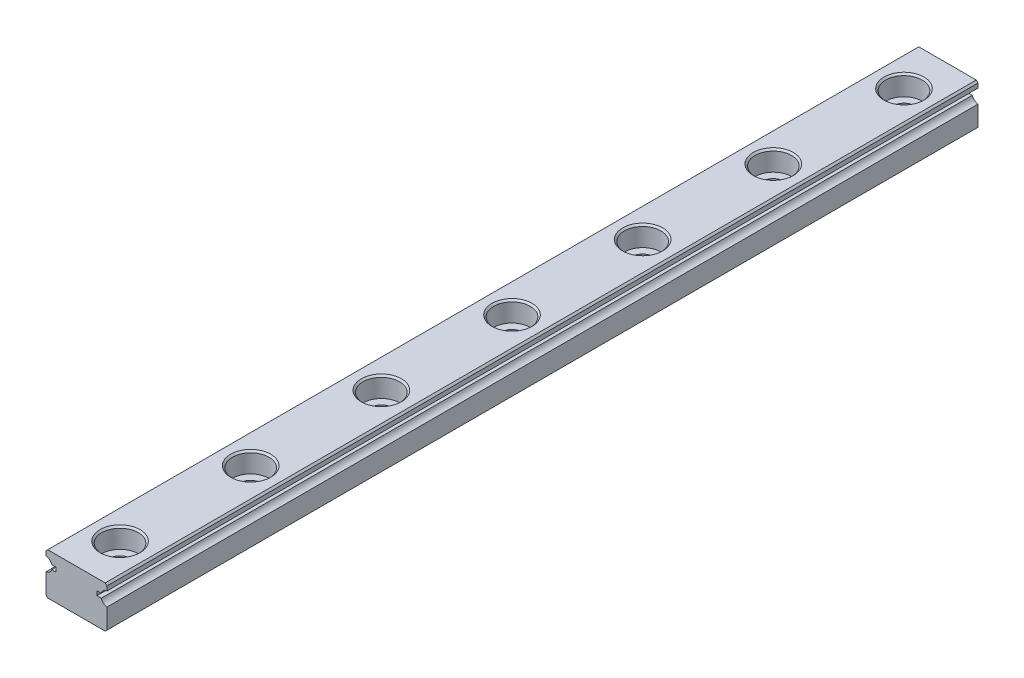
SolidWorks part; units mm, degrees
ref_plane "Спереди" through (0, 0, 0) normal (0, 0, 1) x (1, 0, 0)
ref_plane "Сверху" through (0, 0, 0) normal (0, 1, 0) x (1, 0, 0)
ref_plane "Справа" through (0, 0, 0) normal (1, 0, 0) x (0, 0, -1)
sketch "Sketch1" plane through (0, 0, 0) normal (0, 0, 1) x (1, 0, 0)
  line L0 (0, 0) -> (0, 4.3706) construction
  line L1 (-3.3, -2.4) -> (3.3, -2.4)
  line L2 (-3.5, -2.2) -> (-3.5, 0.1063)
  line L3 (-3.3, 2.4) -> (3.3, 2.4)
  line L4 (3.5, -2.2) -> (3.5, 0.1063)
  line L5 (-3.5, -2.4) -> (3.5, 2.4) construction
  line L6 (-3.5, 2.4) -> (3.5, -2.4) construction
  line L7 (-3.5, 1.6937) -> (-3.5, 2.2)
  line L8 (3.5, 1.6937) -> (3.5, 2.2)
  line L9 (-3.5, -2.2) -> (-3.3, -2.4)
  line L10 (3.3, -2.4) -> (3.5, -2.2)
  line L11 (3.3, 2.4) -> (3.5, 2.2)
  line L12 (-3.5, 2.2) -> (-3.3, 2.4)
  line L13 (2.8401, 0.65) -> (2.3401, 0.65)
  line L14 (-2.8401, 0.65) -> (-2.3401, 0.65)
  line L15 (2.3401, 0.65) -> (2.3401, 1.15)
  line L16 (-2.8401, 1.15) -> (-2.3401, 1.15)
  line L17 (-2.3401, 0.65) -> (-2.3401, 1.15)
  line L18 (2.8401, 1.15) -> (2.3401, 1.15)
  arc A0 (-3.5, 1.6937) -> (-2.8401, 1.15) centre (-3.6, 0.9) cw
  arc A1 (3.5, 1.6937) -> (2.8401, 1.15) centre (3.6, 0.9) ccw
  arc A2 (-2.8401, 0.65) -> (-3.5, 0.1063) centre (-3.6, 0.9) cw
  arc A3 (2.8401, 0.65) -> (3.5, 0.1063) centre (3.6, 0.9) ccw
  point P0 (0, 0)
  dimension "D4" = 0.8
  dimension "D5" = 0.1
  dimension "D1" = 7
  dimension "D2" = 4.8
  dimension "D3" = 1.5
  dimension "D6" = 0.5
  dimension "D7" = 0.5
extrude "Extrude1" add sketch "Sketch1" along normal blind 150
sketch "Sketch2" plane through (0, 2.4, 0) normal (0, 1, 0) x (1, 0, 0)
  line L0 (0, 0) -> (0, -5) construction
  circle A0 centre (0, -5) radius 1.2
  circle A1 centre (0, -5) radius 2.1
  dimension "D1" = 2.4
  dimension "D2" = 4.2
  dimension "D3" = 5
extrude "Extrude2" cut sketch "Sketch2" against normal up to next contours A0 region at (0, 2.4, 5)
extrude "Extrude4" cut sketch "Sketch" against normal blind 2.3
sketch "Sketch" plane through (0, 2.4, 0) normal (0, 1, 0) x (1, 0, 0) same geometry as "Sketch2"
chamfer "Chamfer1" distance 0.2 angle 45 2 edges at (0, -2.4, 6.2) (0, 2.4, 7.1)
pattern_linear "LPattern1" count 10 spacing 15 along (0, 0, 1) of "Extrude4", "Chamfer1", "Extrude2"
sketch "Sketch3" plane through (0, 0, 0) normal (0, 0, -1) x (-1, 0, 0)
  line L1 (-5.0194, 4.0018) -> (4.6867, 4.0018)
  line L2 (-5.0194, 4.0018) -> (-5.0194, -3.2386)
  line L3 (-5.0194, -3.2386) -> (4.6867, -3.2386)
  line L4 (4.6867, 4.0018) -> (4.6867, -3.2386)
extrude "Cut-Extrude2" cut sketch "Sketch3" against normal blind 30
sketch "Sketch4" plane through (0, 0, 150) normal (0, 0, 1) x (1, 0, 0)
  line L1 (-4.0776, 2.8823) -> (4.2978, 2.8823)
  line L2 (-4.0776, 2.8823) -> (-4.0776, -2.9216)
  line L3 (-4.0776, -2.9216) -> (4.2978, -2.9216)
  line L4 (4.2978, 2.8823) -> (4.2978, -2.9216)
extrude "Cut-Extrude3" cut sketch "Sketch4" against normal blind 20
